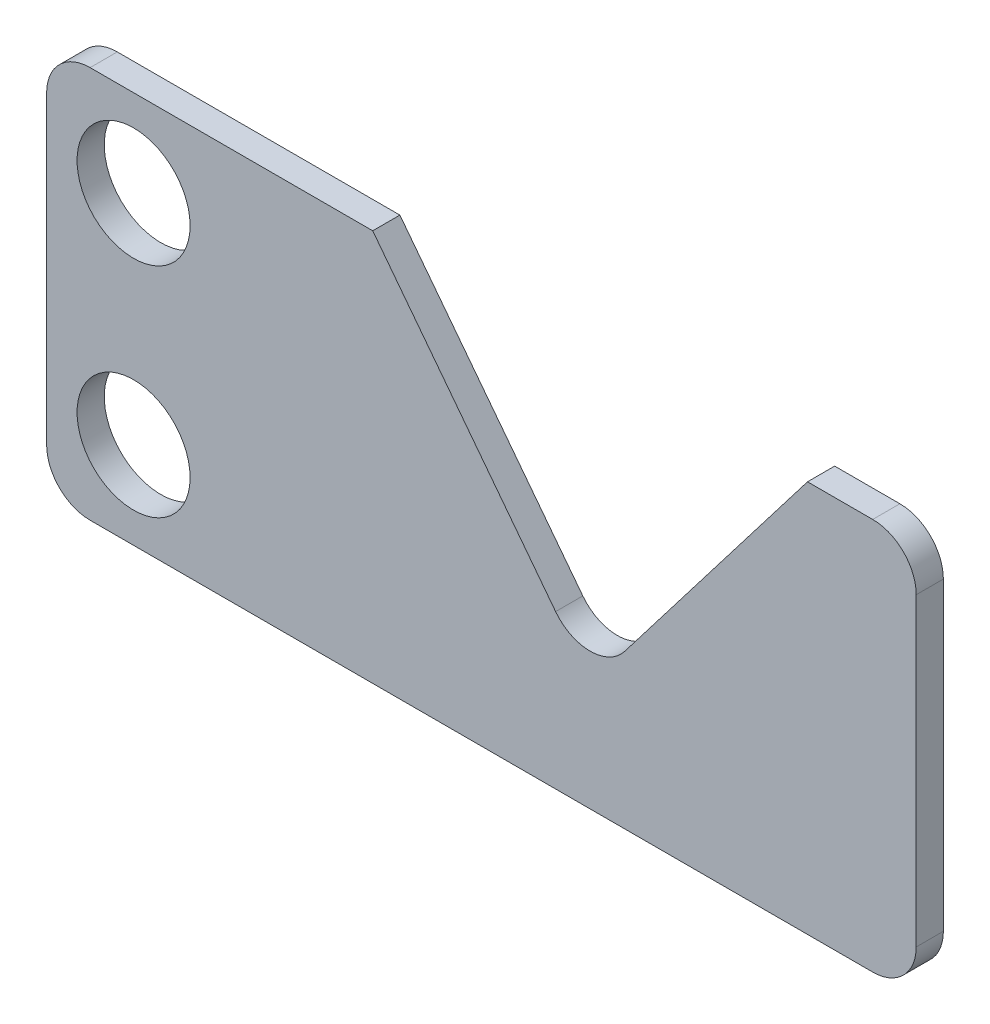
SolidWorks part; units mm, degrees
ref_plane "Front Plane" through (0, 0, 0) normal (0, 0, 1) x (1, 0, 0)
ref_plane "Top Plane" through (0, 0, 0) normal (0, 1, 0) x (1, 0, 0)
ref_plane "Right Plane" through (0, 0, 0) normal (1, 0, 0) x (0, 0, -1)
sketch "Sketch2" plane through (0, 0, 0) normal (0, 0, 1) x (1, 0, 0)
  line L0 (19.05, 22.901) -> (29.7349, 8.9762)
  line L1 (2.54, 0) -> (48.26, 0)
  line L2 (0, 2.54) -> (0, 20.361)
  line L3 (2.54, 22.901) -> (19.05, 22.901)
  line L4 (50.8, 2.54) -> (50.8, 20.361)
  line L5 (33.7651, 8.9762) -> (44.45, 22.901)
  line L6 (44.45, 22.901) -> (48.26, 22.901)
  circle A1 centre (5.08, 17.821) radius 3.302
  circle A2 centre (5.08, 5.08) radius 3.302
  arc A3 (2.54, 0) -> (0, 2.54) centre (2.54, 2.54) cw
  arc A4 (0, 20.361) -> (2.54, 22.901) centre (2.54, 20.361) cw
  arc A5 (29.7349, 8.9762) -> (33.7651, 8.9762) centre (31.75, 10.5224) ccw
  arc A6 (48.26, 22.901) -> (50.8, 20.361) centre (48.26, 20.361) cw
  arc A7 (48.26, 0) -> (50.8, 2.54) centre (48.26, 2.54) ccw
  point P18 (0, 0)
  point P23 (31.75, 6.35)
  point P26 (50.8, 22.901)
  point P29 (50.8, 0)
  dimension "D6" = 5.08
  dimension "D9" = 6.604
  dimension "D10" = 6.604
  dimension "D11" = 2.54
  dimension "D1" = 50.8
  dimension "D2" = 6.35
  dimension "D3" = 25.4
  dimension "D4" = 6.35
  dimension "D5" = 75
  dimension "D7" = 5.08
  dimension "D8" = 5.08
extrude "Boss-Extrude1" add sketch "Sketch2" along normal blind 1.5875
